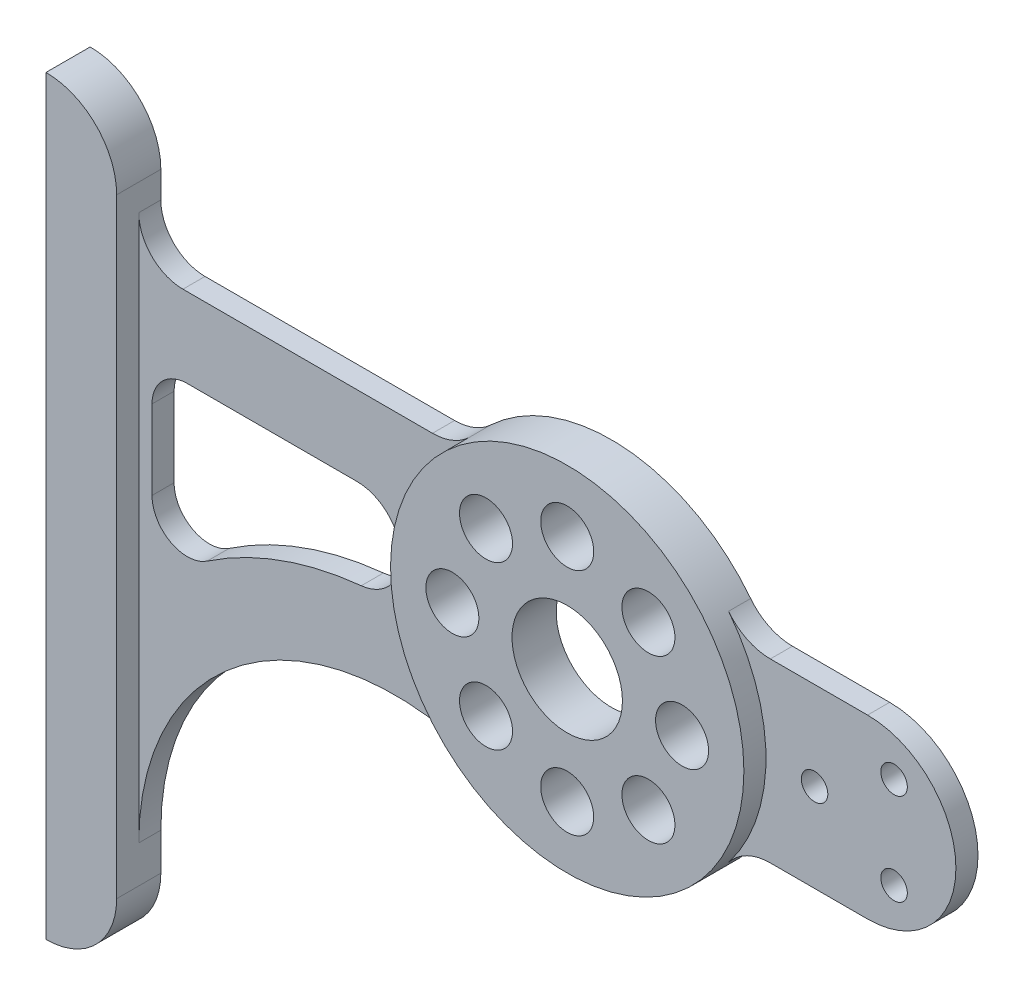
SolidWorks part; units mm, degrees
ref_plane "Спереди" through (0, 0, 0) normal (0, 0, 1) x (1, 0, 0)
ref_plane "Сверху" through (0, 0, 0) normal (0, 1, 0) x (1, 0, 0)
ref_plane "Справа" through (0, 0, 0) normal (1, 0, 0) x (0, 0, -1)
sketch "Эскиз2" plane through (0, 0, 0) normal (0, 0, 1) x (1, 0, 0)
  line L0 (0, 44.7609) -> (0, -57.7174) construction
  line L1 (-40, 0) -> (118.5914, 0) construction
  line L2 (63, 20) -> (40.9878, 20)
  line L3 (63, -20) -> (40.9878, -20)
  line L4 (-40, 0) -> (-152.6249, 0) construction
  line L5 (-102, 42) -> (-102, -96)
  line L6 (-91, 8) -> (-52.6179, 8)
  line L7 (-118, 58) -> (-118, -112)
  line L8 (-92, 26) -> (-35.4965, 26)
  line L9 (-99, -17.9467) -> (-99, 0)
  circle A0 centre (0, 0) radius 40
  circle A1 centre (0, 0) radius 12.5
  circle A2 centre (0, 0) radius 26 construction
  circle A3 centre (0, 26) radius 6
  circle A4 centre (18.3848, 18.3848) radius 6
  circle A5 centre (26, 0) radius 6
  circle A6 centre (18.3848, -18.3848) radius 6
  circle A7 centre (0, -26) radius 6
  circle A8 centre (-18.3848, -18.3848) radius 6
  circle A9 centre (-26, 0) radius 6
  circle A10 centre (-18.3848, 18.3848) radius 6
  circle A11 centre (63, 0) radius 12 construction
  circle A12 centre (51, 0) radius 3
  circle A13 centre (69, 10.3923) radius 3
  circle A14 centre (69, -10.3923) radius 3
  arc A15 (63, -20) -> (63, 20) centre (63, 0) ccw
  arc A16 (31.5291, 24.6154) -> (40.9878, 20) centre (40.9878, 32) ccw
  arc A17 (40.9878, -20) -> (31.5291, -24.6154) centre (40.9878, -32) ccw
  arc A18 (-35.4965, 26) -> (-27.305, 29.2308) centre (-35.4965, 38) ccw
  arc A19 (-102, 36) -> (-92, 26) centre (-92, 36) ccw
  arc A20 (-91, 8) -> (-99, 0) centre (-91, 0) ccw
  arc A21 (-102, 42) -> (-118, 58) centre (-118, 42) ccw
  arc A22 (-118, -112) -> (-102, -96) centre (-118, -96) ccw
  arc A23 (-17.9592, -35.7417) -> (-102, -87.5671) centre (-44, -87.5671) ccw
  arc A24 (-99, -17.9467) -> (-86.5238, -24.5772) centre (-91, -17.9467) ccw
  arc A25 (-51.6158, -11.9497) -> (-86.5238, -24.5772) centre (-44, -87.5671) ccw
  arc A26 (-51.6158, -11.9497) -> (-52.6179, 8) centre (-52.6179, -2) ccw
  point P26 (0, 0)
  point P36 (63, 0)
  dimension "D1" = 80
  dimension "D2" = 25
  dimension "D3" = 52
  dimension "D4" = 12
  dimension "D7" = 24
  dimension "D8" = 6
  dimension "D10" = 20
  dimension "D11" = 12
  dimension "D12" = 12
  dimension "D19" = 12
  dimension "D20" = 10
  dimension "D21" = 8
  dimension "D22" = 16
  dimension "D23" = 16
  dimension "D24" = 58
  dimension "D25" = 76
  dimension "D26" = 8
  dimension "D27" = 10
  dimension "D6" = 63
  dimension "D13" = 58
  dimension "D14" = 170
  dimension "D15" = 118
  dimension "D16" = 16
  dimension "D18" = 18
  dimension "D28" = 3
  dimension "D5" = 8
  dimension "D9" = 3
extrude "Бобышка-Вытянуть1" add sketch "Эскиз2" along normal blind 5 contours A17 L3 A15 L2 A16 A0 A14 A13 A12 | A23 A0 A18 L8 A19 L5 region at (58.2944, 0, 0) region at (-41.0717, -5.9078, 0)
extrude "Бобышка-Вытянуть2" add sketch "Эскиз2<3>" along normal blind 10 contours L7 A22 L5 A21 | A0 A10 A9 A8 A7 A6 A5 A4 A3 A1 region at (36.7532, 12.6479, 0) region at (-110.1863, -27, 0)
sketch "Эскиз2<3>" plane through (0, 0, 0) normal (0, 0, 1) x (1, 0, 0) same geometry as "Эскиз2"
